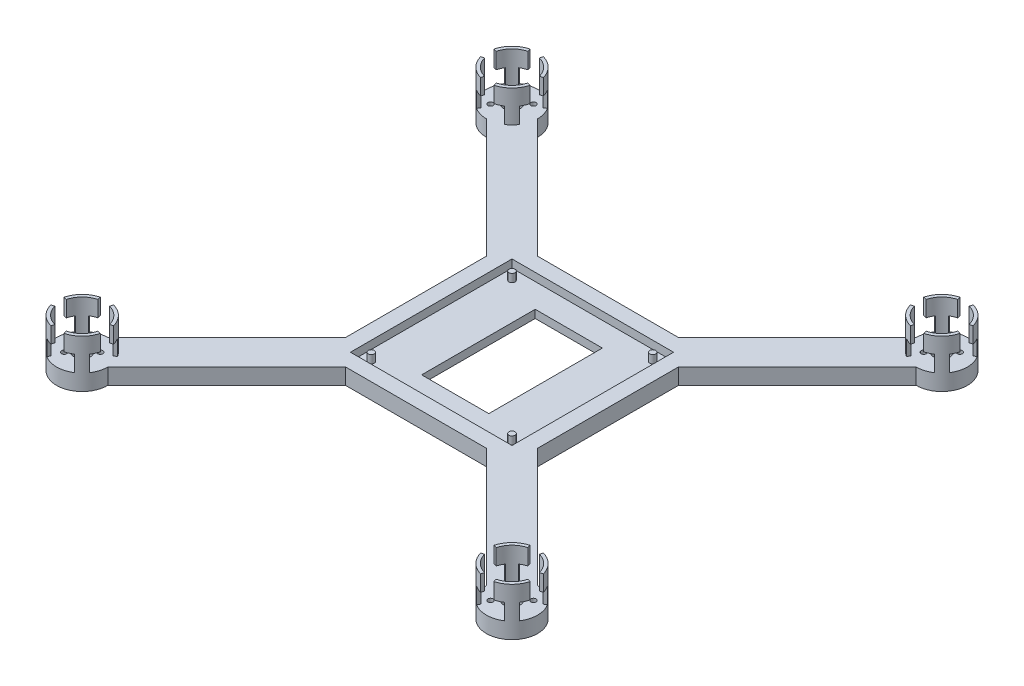
SolidWorks part; units mm, degrees
ref_plane "정면" through (0, 0, 0) normal (0, 0, 1) x (1, 0, 0)
ref_plane "윗면" through (0, 0, 0) normal (0, 1, 0) x (1, 0, 0)
ref_plane "우측면" through (0, 0, 0) normal (1, 0, 0) x (0, 0, -1)
sketch "스케치1" plane through (0, 0, 0) normal (0, 1, 0) x (1, 0, 0)
  line L5 (134.3503, -118.3503) -> (60, -44)
  line L6 (-44, 60) -> (44, 60)
  line L8 (-60, 44) -> (-60, -44)
  line L9 (-44, -60) -> (44, -60)
  line L10 (60, 44) -> (60, -44)
  line L11 (-60, 60) -> (60, -60) construction
  line L18 (-60, -60) -> (60, 60) construction
  line L19 (60, -44) -> (44, -60) construction
  line L20 (44, -60) -> (118.3503, -134.3503)
  line L21 (-118.3503, -134.3503) -> (-44, -60)
  line L22 (-60, -44) -> (-134.3503, -118.3503)
  line L23 (-134.3503, 118.3503) -> (-60, 44)
  line L24 (-44, 60) -> (-118.3503, 134.3503)
  line L25 (118.3503, 134.3503) -> (44, 60)
  line L26 (60, 44) -> (134.3503, 118.3503)
  line L27 (-60, -60) -> (-44, -60) construction
  line L28 (-60, -44) -> (-60, -60) construction
  line L29 (44, -60) -> (60, -60) construction
  line L30 (60, -44) -> (60, -60) construction
  line L31 (44, 60) -> (60, 60) construction
  line L32 (60, 60) -> (60, 44) construction
  line L33 (-60, 60) -> (-44, 60) construction
  line L34 (-60, 60) -> (-60, 44) construction
  line L35 (134.3503, 134.3503) -> (35489.6893, -35220.9888) construction
  line L36 (-134.3503, 134.3503) -> (-35489.6893, -35220.9888) construction
  line L37 (-134.3503, -134.3503) -> (-122.3295, -146.3711) construction
  line L38 (-21, 35.5) -> (21, 35.5)
  line L39 (-21, 35.5) -> (-21, -35.5)
  line L40 (-21, -35.5) -> (21, -35.5)
  line L41 (21, 35.5) -> (21, -35.5)
  line L42 (-21, 35.5) -> (21, -35.5) construction
  line L43 (-21, -35.5) -> (21, 35.5) construction
  line L44 (134.3503, -134.3503) -> (35489.6893, 35220.9888) construction
  arc A5 (118.3503, -134.3503) -> (134.3503, -118.3503) centre (134.3503, -134.3503) ccw
  arc A6 (123.0366, -123.0366) -> (118.3503, -134.3503) centre (134.3503, -134.3503) ccw construction
  arc A7 (134.3503, -118.3503) -> (123.0366, -123.0366) centre (134.3503, -134.3503) ccw construction
  arc A8 (-134.3503, -118.3503) -> (-118.3503, -134.3503) centre (-134.3503, -134.3503) ccw
  arc A9 (-123.0366, -123.0366) -> (-134.3503, -118.3503) centre (-134.3503, -134.3503) ccw construction
  arc A10 (-118.3503, -134.3503) -> (-123.0366, -123.0366) centre (-134.3503, -134.3503) ccw construction
  arc A11 (-118.3503, 134.3503) -> (-134.3503, 118.3503) centre (-134.3503, 134.3503) ccw
  arc A12 (-123.0366, 123.0366) -> (-118.3503, 134.3503) centre (-134.3503, 134.3503) ccw construction
  arc A13 (-134.3503, 118.3503) -> (-123.0366, 123.0366) centre (-134.3503, 134.3503) ccw construction
  arc A14 (134.3503, 118.3503) -> (145.664, 123.0366) centre (134.3503, 134.3503) ccw
  arc A15 (123.0366, 123.0366) -> (134.3503, 118.3503) centre (134.3503, 134.3503) ccw construction
  arc A16 (118.3503, 134.3503) -> (123.0366, 123.0366) centre (134.3503, 134.3503) ccw construction
  circle A49 centre (134.3503, 134.3503) radius 5.1
  circle A50 centre (140.0071, 140.0071) radius 1.65
  circle A51 centre (141.0678, 127.6328) radius 1.65
  circle A53 centre (127.6328, 141.0678) radius 1.65
  circle A54 centre (128.6934, 128.6934) radius 1.65
  circle A58 centre (134.3503, -134.3503) radius 5.1
  circle A59 centre (140.0071, -140.0071) radius 1.65
  circle A60 centre (127.6328, -141.0678) radius 1.65
  circle A61 centre (141.0678, -127.6328) radius 1.65
  circle A62 centre (128.6934, -128.6934) radius 1.65
  circle A63 centre (-134.3503, -134.3503) radius 5.1
  circle A64 centre (134.3503, 134.3503) radius 16 construction
  arc A65 (145.664, 123.0366) -> (145.664, 145.664) centre (134.3503, 134.3503) ccw
  circle A66 centre (134.3503, 134.3503) radius 16 construction
  circle A67 centre (134.3503, 134.3503) radius 16 construction
  arc A68 (123.0366, 145.664) -> (118.3503, 134.3503) centre (134.3503, 134.3503) ccw
  circle A69 centre (134.3503, 134.3503) radius 16 construction
  circle A70 centre (134.3503, 134.3503) radius 16 construction
  arc A71 (145.664, 145.664) -> (123.0366, 145.664) centre (134.3503, 134.3503) ccw
  circle A72 centre (134.3503, 134.3503) radius 16 construction
  circle A75 centre (-140.0071, -140.0071) radius 1.65
  circle A76 centre (-141.0678, -127.6328) radius 1.65
  circle A77 centre (-127.6328, -141.0678) radius 1.65
  circle A78 centre (-128.6934, -128.6934) radius 1.65
  circle A79 centre (-134.3503, 134.3503) radius 5.1
  circle A80 centre (-140.0071, 140.0071) radius 1.65
  circle A81 centre (-127.6328, 141.0678) radius 1.65
  circle A82 centre (-141.0678, 127.6328) radius 1.65
  circle A83 centre (-128.6934, 128.6934) radius 1.65
  point P0 (0, 0)
  point P36 (0, 0)
  point P47 (0, 0)
  point P71 (0, 0)
  point P72 (0, 0)
  dimension "D4" = 190
  dimension "D5" = 71
  dimension "D6" = 42
  dimension "D3" = 4
  dimension "D9" = 8
  dimension "D11" = 3.3
  dimension "D12" = 9.5
  dimension "D13" = 16
  dimension "D15" = 2
  dimension "D7" = 10.2
  dimension "D10" = 3.3
  dimension "D16" = 9.5
  dimension "D1" = 120
  dimension "D2" = 120
  dimension "D8" = 4
extrude "보스-돌출2" add sketch "스케치1" against normal blind 10
sketch "스케치2" plane through (0, 0, 0) normal (0, 1, 0) x (1, 0, 0)
  line L1 (-50.5, 50.5) -> (50.5, 50.5)
  line L2 (-50.5, 50.5) -> (-50.5, -50.5)
  line L3 (-50.5, -50.5) -> (50.5, -50.5)
  line L4 (50.5, 50.5) -> (50.5, -50.5)
  line L5 (-50.5, 50.5) -> (50.5, -50.5) construction
  line L6 (-50.5, -50.5) -> (50.5, 50.5) construction
  point P0 (0, 0)
  dimension "D1" = 101
  dimension "D2" = 101
extrude "컷-돌출1" cut sketch "스케치2" against normal blind 5
sketch "스케치3" plane through (0, 0, 0) normal (0, 1, 0) x (1, 0, 0)
  line L1 (-44, 44) -> (44, 44) construction
  line L2 (-44, 44) -> (-44, -44) construction
  line L3 (-44, -44) -> (44, -44) construction
  line L4 (44, 44) -> (44, -44) construction
  line L5 (-44, 44) -> (44, -44) construction
  line L6 (-44, -44) -> (44, 44) construction
  circle A0 centre (-44, 44) radius 1.9
  circle A1 centre (44, 44) radius 1.9
  circle A2 centre (-44, -44) radius 1.9
  circle A3 centre (44, -44) radius 1.9
  point P0 (0, 0)
  dimension "D3" = 3.8
  dimension "D1" = 88
  dimension "D2" = 88
extrude "보스-돌출3" add sketch "스케치3" along normal blind 5 from surface starting at face at (0, -5, 0)
sketch "스케치5" plane through (0, 0, 0) normal (0, 1, 0) x (1, 0, 0)
  line L0 (134.5732, 134.1274) -> (35489.9122, -35221.2117) construction
  line L1 (134.3503, 134.3503) -> (35489.6893, 35489.6893) construction
  line L2 (-865.6497, 134.3503) -> (49134.3503, 134.3503) construction
  circle A0 centre (134.3503, 134.3503) radius 16
  circle A1 centre (134.3503, 134.3503) radius 14
  point P0 (0, 0)
  dimension "D1" = 32
  dimension "D2" = 28
  dimension "D3" = 45
  dimension "D4" = 45
extrude "보스-돌출4" add sketch "스케치5" along normal blind 20
sketch "스케치6" plane through (0, 0, 0) normal (0, 1, 0) x (1, 0, 0)
  line L0 (697.887, -730.2018) -> (143.0873, 120.9464) construction
  line L1 (972.0946, -411.7124) -> (134.3503, 134.3503) construction
  line L2 (134.3503, 134.3503) -> (134.3503, -49865.6497) construction
  line L3 (-730.2018, -429.1865) -> (120.9464, 125.6133) construction
  line L4 (-429.1865, -730.2018) -> (125.6133, 120.9464) construction
  line L9 (125.6133, 147.7542) -> (134.3503, 134.3503)
  line L10 (147.7542, 125.6133) -> (134.3503, 134.3503)
  line L11 (134.3503, 134.3503) -> (147.7542, 143.0873)
  line L12 (143.0873, 147.7542) -> (134.3503, 134.3503)
  line L13 (120.9464, 143.0873) -> (-41752.864, 27437.4872) construction
  line L14 (134.3503, 134.3503) -> (42021.5645, 27437.4872) construction
  line L15 (134.3503, 134.3503) -> (-27168.7866, 42021.5645) construction
  line L16 (134.3503, 134.3503) -> (27437.4872, 42021.5645) construction
  line L17 (143.0873, 120.9464) -> (134.3503, 134.3503)
  line L18 (125.6133, 120.9464) -> (134.3503, 134.3503)
  line L19 (120.9464, 125.6133) -> (134.3503, 134.3503)
  line L20 (120.9464, 143.0873) -> (134.3503, 134.3503)
  circle A0 centre (134.3503, 134.3503) radius 16 construction
  arc A1 (120.9464, 143.0873) -> (120.9464, 125.6133) centre (134.3503, 134.3503) ccw
  arc A2 (143.0873, 147.7542) -> (125.6133, 147.7542) centre (134.3503, 134.3503) ccw
  arc A3 (147.7542, 125.6133) -> (147.7542, 143.0873) centre (134.3503, 134.3503) ccw
  arc A4 (125.6133, 120.9464) -> (143.0873, 120.9464) centre (134.3503, 134.3503) ccw
  circle A5 centre (140.0071, 140.0071) radius 1.65 construction
extrude "컷-돌출2" cut sketch "스케치6" along normal blind 10 contours L20 A1 L19 | L18 A4 L17 | L10 A3 L11 | L12 A2 L9 region at (134.3503, 0, -144.4336) region at (144.4336, 0, -134.3503) region at (134.3503, 0, -124.267) region at (124.267, 0, -134.3503)
sketch "스케치8" plane through (0, 0, 0) normal (0, 1, 0) x (1, 0, 0)
  line L0 (134.3503, 134.3503) -> (118.8955, 130.2092)
  line L1 (134.3503, 134.3503) -> (118.8955, 138.4914)
  line L2 (134.3503, 134.3503) -> (149.8051, 130.2092)
  line L3 (134.3503, 134.3503) -> (149.8051, 138.4914)
  line L4 (134.3503, 134.3503) -> (138.4914, 118.8955)
  line L5 (134.3503, 134.3503) -> (130.2092, 118.8955)
  line L6 (134.3503, 134.3503) -> (138.4914, 149.8051)
  line L7 (134.3503, 134.3503) -> (130.2092, 149.8051)
  line L8 (136.3657, 134.3503) -> (50136.3657, 134.3503) construction
  line L9 (134.3503, 138.8006) -> (134.3503, 50138.8006) construction
  circle A0 centre (134.3503, 134.3503) radius 16 construction
  arc A1 (118.8955, 138.4914) -> (118.8955, 130.2092) centre (134.3503, 134.3503) ccw
  arc A2 (138.4914, 149.8051) -> (130.2092, 149.8051) centre (134.3503, 134.3503) ccw
  arc A3 (149.8051, 130.2092) -> (149.8051, 138.4914) centre (134.3503, 134.3503) ccw
  arc A4 (130.2092, 118.8955) -> (138.4914, 118.8955) centre (134.3503, 134.3503) ccw
  point P2 (118.3503, 134.3503)
  point P11 (134.3503, 150.3503)
  dimension "D1" = 30
  dimension "D2" = 30
extrude "컷-돌출3" cut sketch "스케치8" along normal through all contours L1 A1 L0 | L2 A3 L3 | L6 A2 L7 | L5 A4 L4 region at (123.8051, 0, -134.3503) region at (144.8955, 0, -134.3503) region at (134.3503, 0, -123.8051) region at (134.3503, 0, -144.8955)
ref_axis "기준축1" through (0, 21.5, 0) along (0, -1, 0)
pattern_circular "원형 패턴4" count 4 over 360 about axis through (0, 21.5, 0) along (0, -1, 0) of "보스-돌출4", "컷-돌출3", "컷-돌출2"
ref_plane "평면1" through (0, 0, 0) normal (-0.7071, 0, -0.7071) x (-0.7071, 0, 0.7071)
